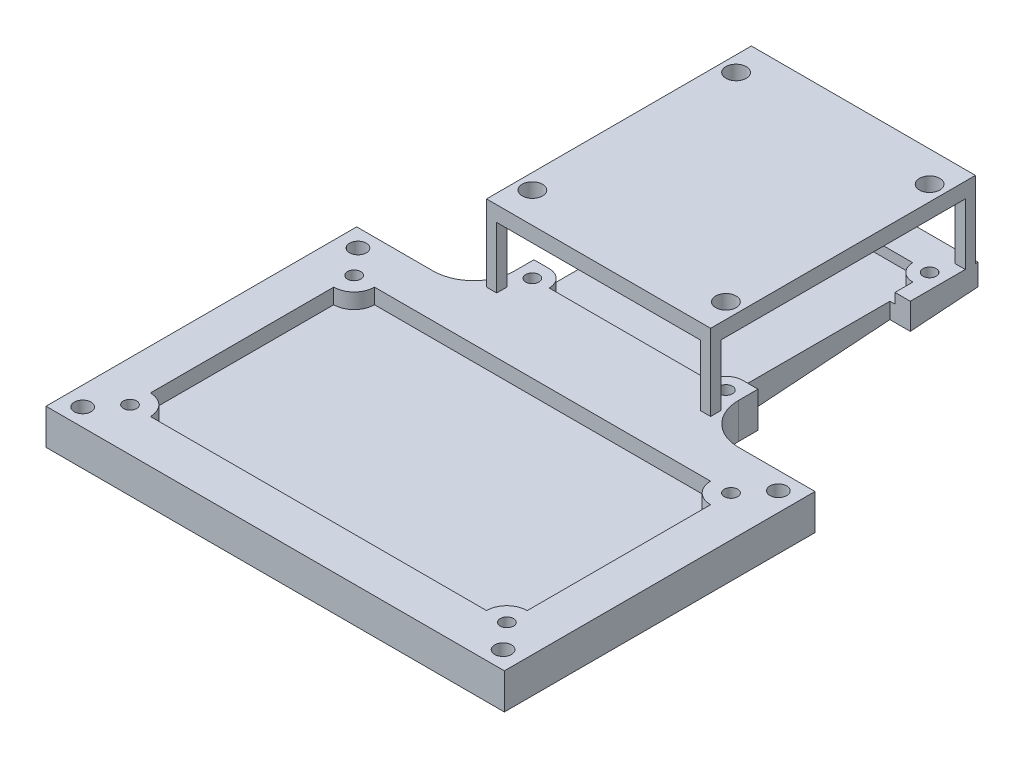
SolidWorks part; units mm, degrees
ref_plane "Front Plane" through (0, 0, 0) normal (0, 0, 1) x (1, 0, 0)
ref_plane "Top Plane" through (0, 0, 0) normal (0, 1, 0) x (1, 0, 0)
ref_plane "Right Plane" through (0, 0, 0) normal (1, 0, 0) x (0, 0, -1)
sketch "Sketch1" plane through (0, 0, 0) normal (0, 1, 0) x (1, 0, 0)
  line L0 (0, 0) -> (90, 0)
  line L1 (90, 0) -> (90, 61)
  line L2 (90, 61) -> (75, 61)
  line L3 (0, 61) -> (0, 0)
  line L4 (86.275, 3.475) -> (86.275, 57.525) construction
  line L5 (86.275, 57.525) -> (3.725, 57.525) construction
  line L6 (15, 61) -> (0, 61)
  line L8 (23, 69) -> (23, 116)
  line L9 (23, 116) -> (67, 116)
  line L10 (67, 69) -> (67, 116)
  line L11 (0, 30.5) -> (90, 30.5) construction
  circle A0 centre (3.725, 57.525) radius 1.65
  circle A1 centre (86.275, 57.525) radius 1.65
  circle A2 centre (86.275, 3.475) radius 1.65
  circle A3 centre (3.725, 3.475) radius 1.65
  arc A4 (15, 61) -> (23, 69) centre (15, 69) ccw
  arc A5 (75, 61) -> (67, 69) centre (75, 69) cw
  point P12 (86.275, 30.5)
  point P13 (90, 30.5)
  point P14 (45, 57.525)
  point P21 (45, 116)
  point P23 (23, 61)
  point P26 (45, 0)
  dimension "D5" = 3.3
  dimension "D6" = 3.3
  dimension "D7" = 3.3
  dimension "D8" = 44
  dimension "D10" = 8
  dimension "D11" = 8
  dimension "D1" = 61
  dimension "D2" = 90
  dimension "D3" = 82.55
  dimension "D4" = 54.05
  dimension "D9" = 55
extrude "Boss-Extrude1" add sketch "Sketch1" along normal blind 7
chamfer "Chamfer1" distance 40 angle 4 1 edges at (45, 0, -116) first distance on face at (86.275, 0, -1.825)
sketch "Sketch2" plane through (0, 7, 0) normal (0, 1, 0) x (1, 0, 0)
  line L0 (0, 0) -> (90, 0) construction
  line L1 (8, 52.5) -> (82, 52.5) construction
  line L2 (8, 52.5) -> (8, 8.5) construction
  line L3 (8, 8.5) -> (82, 8.5) construction
  line L4 (82, 52.5) -> (82, 8.5) construction
  line L5 (0, 61) -> (0, 0) construction
  circle A0 centre (8, 52.5) radius 1.3
  circle A1 centre (8, 8.5) radius 1.3
  circle A2 centre (82, 52.5) radius 1.3
  circle A3 centre (82, 8.5) radius 1.3
  point P10 (45, 0)
  point P11 (45, 8.5)
  point P14 (0, 30.5)
  point P15 (8, 30.5)
  dimension "D3" = 2.6
  dimension "D4" = 2.6
  dimension "D5" = 2.6
  dimension "D6" = 2.6
  dimension "D1" = 74
  dimension "D2" = 44
extrude "Cut-Extrude1" cut sketch "Sketch2" against normal through all
sketch "Sketch3" plane through (0, 7, 0) normal (0, 1, 0) x (1, 0, 0)
  line L0 (67, 116) -> (23, 116) construction
  line L1 (26, 109.5) -> (64, 109.5) construction
  line L2 (26, 109.5) -> (26, 69.5) construction
  line L3 (26, 69.5) -> (64, 69.5) construction
  line L4 (64, 109.5) -> (64, 69.5) construction
  line L5 (23, 116) -> (23, 69) construction
  circle A0 centre (26, 109.5) radius 1.3
  circle A1 centre (64, 109.5) radius 1.3
  circle A2 centre (26, 69.5) radius 1.3
  circle A3 centre (64, 69.5) radius 1.3
  dimension "D3" = 6.5
  dimension "D1" = 40
  dimension "D2" = 38
  dimension "D4" = 3
extrude "Cut-Extrude2" cut sketch "Sketch3" against normal through all
sketch "Sketch4" plane through (0, 7, 0) normal (0, 1, 0) x (1, 0, 0)
  line L1 (12, 52.5) -> (78, 52.5)
  line L2 (8, 48.5) -> (8, 12.5)
  line L3 (12, 8.5) -> (78, 8.5)
  line L4 (82, 48.5) -> (82, 12.5)
  arc A0 (8, 48.5) -> (12, 52.5) centre (8, 52.5) ccw
  arc A1 (78, 52.5) -> (82, 48.5) centre (82, 52.5) ccw
  arc A2 (82, 12.5) -> (78, 8.5) centre (82, 8.5) ccw
  arc A3 (12, 8.5) -> (8, 12.5) centre (8, 8.5) ccw
extrude "Cut-Extrude3" cut sketch "Sketch4" against normal blind 3
sketch "Sketch5" plane through (0, 7, 0) normal (0, 1, 0) x (1, 0, 0)
  line L0 (29.3, 109.5) -> (60.7, 109.5)
  line L5 (45, 106) -> (45, 71.9475) construction
  line L6 (20.5, 89.5) -> (57.0983, 89.5) construction
  line L7 (26, 106.2) -> (26, 72.8)
  line L8 (64, 106.2) -> (64, 72.8)
  line L9 (29.3, 69.5) -> (60.7, 69.5)
  circle A4 centre (26, 109.5) radius 1.3 construction
  arc A5 (26, 106.2) -> (29.3, 109.5) centre (26, 109.5) ccw
  circle A6 centre (26, 69.5) radius 1.3 construction
  circle A7 centre (64, 109.5) radius 1.3 construction
  arc A8 (26, 72.8) -> (29.3, 69.5) centre (26, 69.5) cw
  arc A9 (60.7, 69.5) -> (64, 72.8) centre (64, 69.5) cw
  arc A10 (64, 106.2) -> (60.7, 109.5) centre (64, 109.5) cw
  point P24 (26, 89.5)
  point P25 (45, 109.5)
  dimension "D1" = 3.3
  dimension "D2" = 3.3
  dimension "D3" = 3.3
  dimension "D4" = 3.3
extrude "Cut-Extrude4" cut sketch "Sketch5" against normal blind 2
sketch "Sketch6" plane through (0, 7, 0) normal (0, 1, 0) x (1, 0, 0)
  line L0 (23, 116) -> (23, 69) construction
  line L1 (27, 102.7) -> (23, 102.7)
  line L2 (27, 102.7) -> (27, 72.8)
  line L3 (27, 72.8) -> (23, 72.8)
  line L4 (23, 102.7) -> (23, 72.8)
  line L5 (45, 109.5) -> (45, 69.5) construction
  line L6 (60.7, 109.5) -> (29.3, 109.5) construction
  line L7 (29.3, 69.5) -> (60.7, 69.5) construction
  line L8 (63, 72.8) -> (67, 72.8)
  line L9 (67, 102.7) -> (67, 72.8)
  line L10 (63, 102.7) -> (67, 102.7)
  line L11 (63, 102.7) -> (63, 72.8)
  dimension "D1" = 4
extrude "Cut-Extrude5" cut sketch "Sketch6" against normal through all
sketch "Sketch7" plane through (0, 7, 0) normal (0, 1, 0) x (1, 0, 0)
  line L0 (67, 102.7) -> (67, 116) construction
  line L1 (23, 115.5) -> (67, 115.5)
  line L2 (23, 115.5) -> (23, 63.5)
  line L3 (23, 63.5) -> (67, 63.5)
  line L4 (67, 115.5) -> (67, 63.5)
  circle A1 centre (64, 109.5) radius 1.3 construction
  circle A2 centre (64, 69.5) radius 1.3 construction
  circle A3 centre (26, 109.5) radius 2
  circle A5 centre (64, 109.5) radius 2
  circle A6 centre (64, 69.5) radius 2
  circle A7 centre (26, 69.5) radius 2
  dimension "D2" = 6
  dimension "D1" = 6
extrude "Boss-Extrude2" add sketch "Sketch7" along normal blind 15
sketch "Sketch8" plane through (67, 0, 0) normal (1, 0, 0) x (0, 0, -1)
  line L0 (63.5, 22) -> (115.5, 22) construction
  line L1 (65.5, 7) -> (113.5, 7)
  line L2 (65.5, 7) -> (65.5, 19)
  line L3 (65.5, 19) -> (113.5, 19)
  line L4 (113.5, 7) -> (113.5, 19)
  line L5 (63.5, 22) -> (63.5, 7) construction
  line L6 (115.5, 22) -> (115.5, 7) construction
  dimension "D1" = 3
  dimension "D2" = 2
  dimension "D3" = 2
extrude "Cut-Extrude6" cut sketch "Sketch8" against normal through all
sketch "Sketch9" plane through (0, 0, -115.5) normal (0, 0, -1) x (-1, 0, 0)
  line L1 (-65, 7) -> (-25, 7)
  line L2 (-65, 7) -> (-65, 19)
  line L3 (-65, 19) -> (-25, 19)
  line L4 (-25, 7) -> (-25, 19)
  line L5 (-67, 22) -> (-67, 7) construction
  line L6 (-23, 22) -> (-23, 7) construction
  line L7 (-67, 22) -> (-23, 22) construction
  dimension "D1" = 2
  dimension "D2" = 2
  dimension "D3" = 3
extrude "Cut-Extrude7" cut sketch "Sketch9" against normal through all
equation "\"D4@Sketch2\"=\"D3@Sketch2\""
equation "\"D5@Sketch2\"=\"D3@Sketch2\""
equation "\"D6@Sketch2\"=\"D3@Sketch2\""
